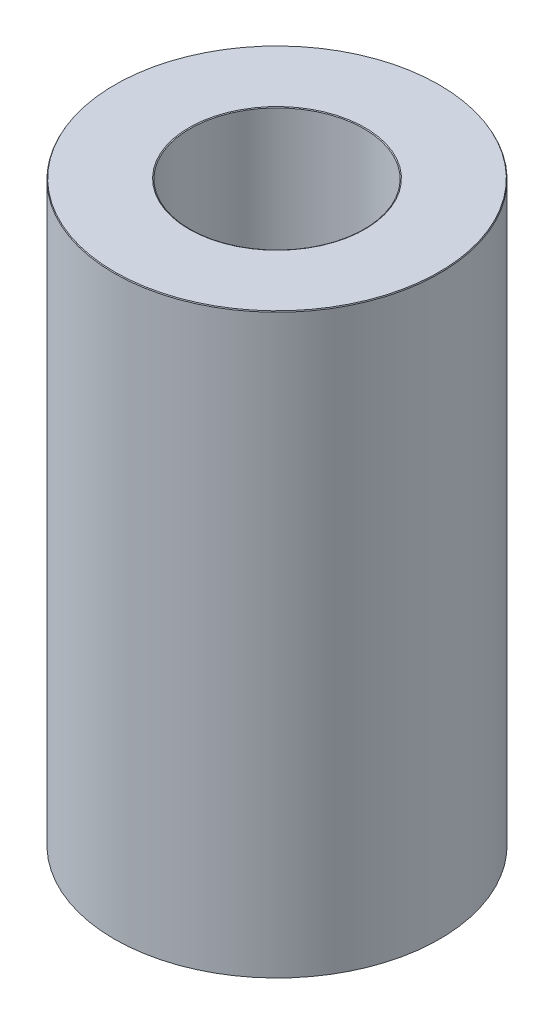
SolidWorks part; units mm, degrees
ref_plane "Front Plane" through (0, 0, 0) normal (0, 0, 1) x (1, 0, 0)
ref_plane "Top Plane" through (0, 0, 0) normal (0, 1, 0) x (1, 0, 0)
ref_plane "Right Plane" through (0, 0, 0) normal (1, 0, 0) x (0, 0, -1)
sketch "Sketch1" plane through (0, 0, 0) normal (0, 1, 0) x (1, 0, 0)
  circle A0 centre (0, 0) radius 47.5
  dimension "SLEEVE_OD" = 95
extrude "Boss-Extrude1" add sketch "Sketch1" along normal blind 168.7352
sketch "Sketch2" plane through (0, 0, 0) normal (0, 1, 0) x (1, 0, 0)
  circle A0 centre (0, 0) radius 25.4273
  dimension "BORE_D" = 50.8546
extrude "Cut-Extrude1" cut sketch "Sketch2" along normal through all
chamfer "Chamfer1" distance 0.2614 angle 30 4 edges at (0, 168.7352, 25.4273) (0, 0, 25.4273) (0, 0, 47.5) (0, 168.7352, 47.5) first distance on face at (0, 168.7352, 25.4273) first distance on face at (0, 0, 25.4273) first distance on face at (0, 168.7352, 47.5)
